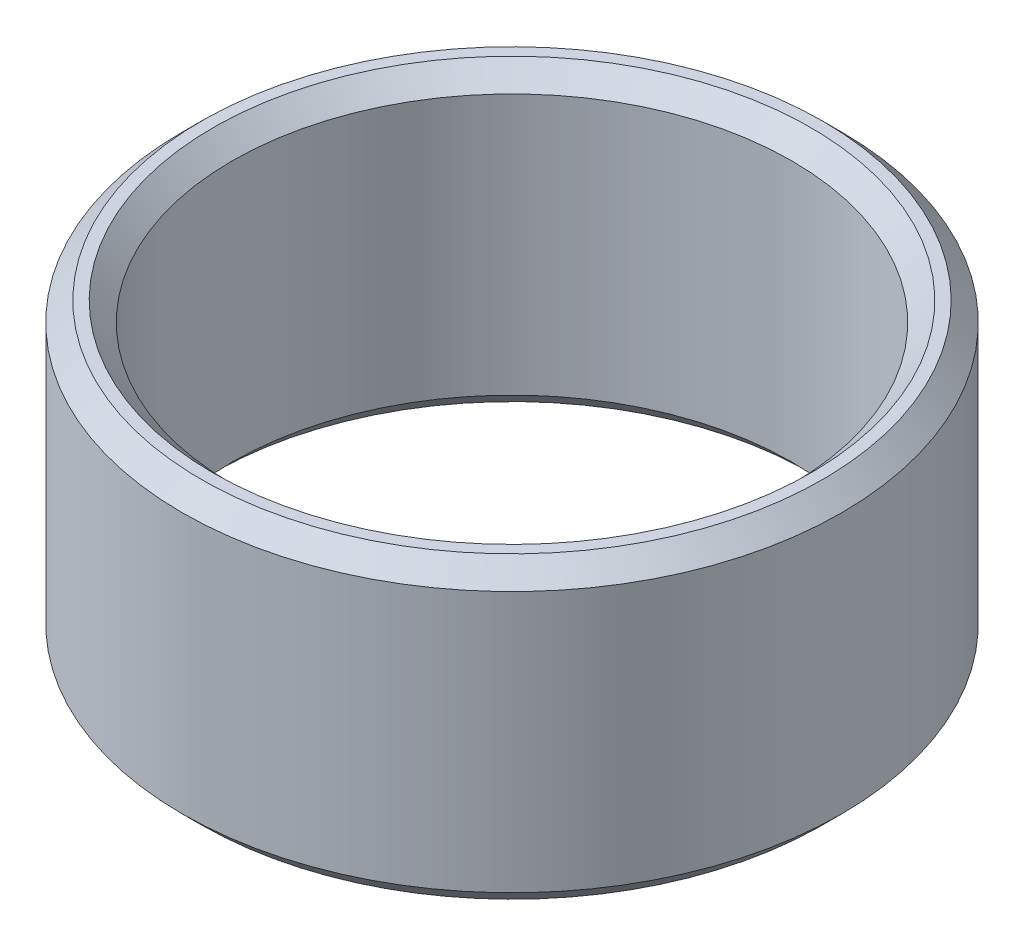
SolidWorks part; units mm, degrees
ref_plane "Front Plane" through (0, 0, 0) normal (0, 0, 1) x (1, 0, 0)
ref_plane "Top Plane" through (0, 0, 0) normal (0, 1, 0) x (1, 0, 0)
ref_plane "Right Plane" through (0, 0, 0) normal (1, 0, 0) x (0, 0, -1)
sketch "Sketch1" plane through (0, 0, 0) normal (0, 1, 0) x (1, 0, 0)
  circle A0 centre (0, 0) radius 30
  dimension "SLEEVE_OD" = 60
extrude "Boss-Extrude1" add sketch "Sketch1" along normal blind 27.2183
sketch "Sketch2" plane through (0, 0, 0) normal (0, 1, 0) x (1, 0, 0)
  circle A0 centre (0, 0) radius 25.4623
  dimension "BORE_D" = 50.9246
extrude "Cut-Extrude1" cut sketch "Sketch2" along normal through all
chamfer "Chamfer1" distance 1.7425 angle 45 4 edges at (0, 27.2183, 25.4623) (0, 0, 25.4623) (0, 0, 30) (0, 27.2183, 30)
